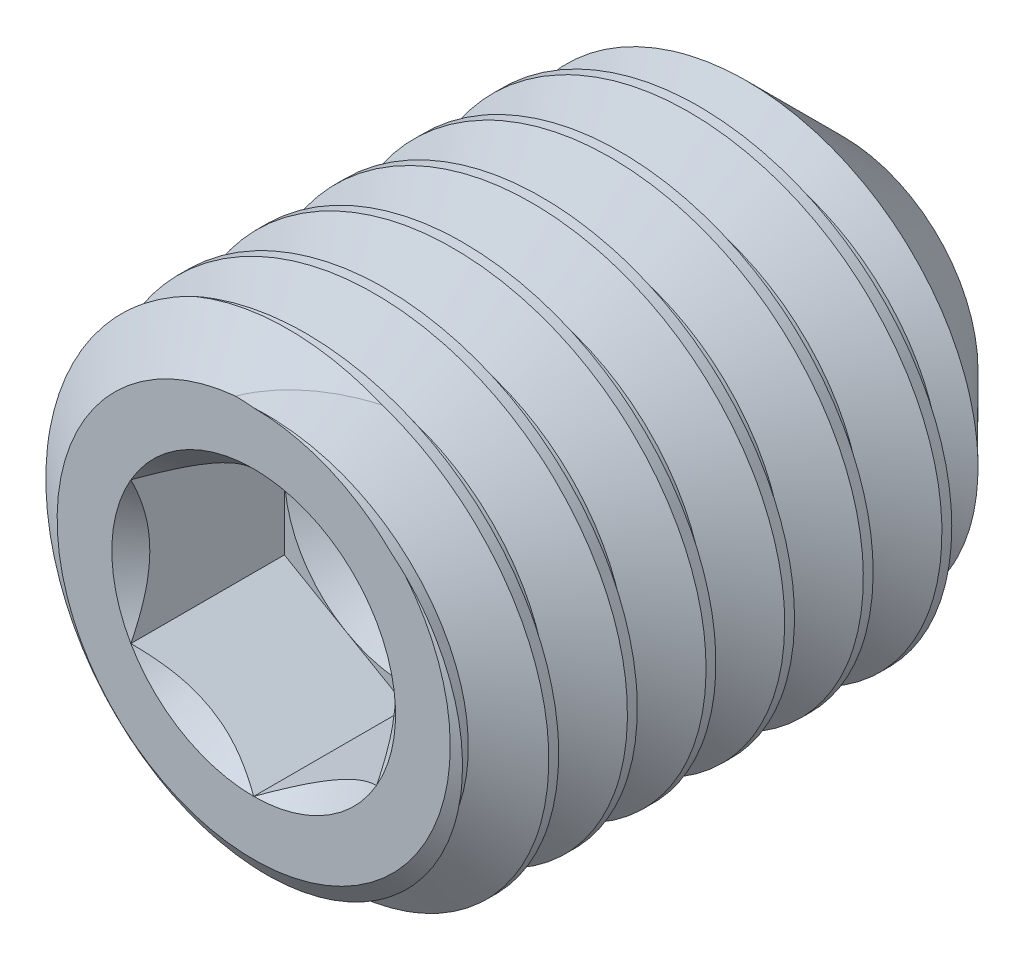
SolidWorks part; units mm, degrees
ref_plane "Front" through (0, 0, 0) normal (0, 0, 1) x (1, 0, 0)
ref_plane "Top" through (0, 0, 0) normal (0, 1, 0) x (1, 0, 0)
ref_plane "Right" through (0, 0, 0) normal (1, 0, 0) x (0, 0, -1)
sketch "Sketch22" plane through (0, 0, 0) normal (1, 0, 0) x (0, 0, -1)
  line L0 (-2.5884, 0) -> (-2.5884, 2)
  line L1 (-2.5884, 2) -> (-2.2383, 2.5)
  line L2 (-2.2383, 2.5) -> (2.2815, 2.5)
  line L3 (2.2815, 2.5) -> (3.4116, 1.3699)
  line L4 (3.4116, 1.3699) -> (2.5884, 0)
  line L5 (2.5884, 0) -> (-2.5884, 0)
  line L6 (2.5884, 0) -> (3.4116, 0) construction
  line L7 (3.4116, 0) -> (3.4116, 1.3699) construction
  line L8 (3.4116, -1.3699) -> (2.5884, 0) construction
  line L9 (-2.2383, -2.5) -> (2.2815, -2.5) construction
  dimension "Dia" = 5
  dimension "Length" = 6
  dimension "D3" = 35
  dimension "D5" = 118
  dimension "D6" = 45
  dimension "D7" = 4
revolve "Revolve1" add sketch "Sketch22" angle 360 about L6
ref_plane "Plane1" through (0, 0, -3.4116) normal (0, 0, 1) x (1, 0, 0)
sketch "Sketch27" plane through (0, 0, -3.4116) normal (0, 0, 1) x (1, 0, 0)
  circle A0 centre (0, 0) radius 2.5 construction
  circle A1 centre (0, 0) radius 2.5
curve "Helix/Spiral1" pitch 0.8 height 6.8 radius 2.5 centre (0, 0, -3.4116) axis (0, 0, 1) start towards (0, 1, 0)
sketch "Sketch28" plane through (0, 0, 0) normal (1, 0, 0) x (0, 0, -1)
  line L0 (3.4116, 2.5) -> (4.1116, 2.5)
  line L1 (4.1116, 2.5) -> (3.8116, 1.9804)
  line L2 (3.8116, 1.9804) -> (3.7116, 1.9804)
  line L3 (3.7116, 1.9804) -> (3.4116, 2.5)
  line L4 (3.5616, 2.2402) -> (3.9616, 2.2402) construction
  line L6 (-2.2383, 2.5) -> (2.2815, 2.5) construction
  dimension "D1" = 0.1
  dimension "D3" = 60
  dimension "D2" = 0.4
sweep "Cut-Sweep2" cut profiles "Sketch28" path "Helix/Spiral1" align with end faces yes
sketch "Sketch23" plane through (0, 0, 2.5884) normal (0, 0, 1) x (1, 0, 0)
  line L1 (0, 1.4434) -> (-1.25, 0.7217)
  line L2 (-1.25, 0.7217) -> (-1.25, -0.7217)
  line L3 (-1.25, -0.7217) -> (0, -1.4434)
  line L4 (0, -1.4434) -> (1.25, -0.7217)
  line L5 (1.25, -0.7217) -> (1.25, 0.7217)
  line L6 (1.25, 0.7217) -> (0, 1.4434)
  circle A0 centre (0, 0) radius 1.25 construction
  dimension "Hex" = 2.5
extrude "Cut-Extrude10" cut sketch "Sketch23" against normal blind 1.5625
sketch "Sketch24" plane through (0, 0, 2.5884) normal (0, 0, 1) x (1, 0, 0)
  circle A0 centre (0, 0) radius 1.4434
extrude "Cut-Extrude11" cut sketch "Sketch24" against normal through all draft 45
sketch "Sketch26" plane through (0, 0, 1.0259) normal (0, 0, 1) x (1, 0, 0)
  circle A0 centre (0, 0) radius 1.25 construction
  circle A1 centre (0, 0) radius 1.25
extrude "Cut-Extrude12" cut sketch "Sketch26" against normal through all draft 60
sketch "Sketch30" plane through (0, 0, 0) normal (1, 0, 0) x (0, 0, -1)
  line L0 (-2.2383, 2.5) -> (2.2815, 2.5) construction
  line L1 (-2.5884, 0) -> (-2.5884, 2) construction
  line L2 (3.4116, 0) -> (3.4116, 1.3699) construction
  line L3 (-2.2383, -2.5) -> (2.2815, -2.5) construction
  point P0 (-2.5884, 2.5)
  point P1 (3.4116, 2.5)
  point P2 (3.4116, -2.5)
  point P11 (2.2116, -2.5)
  dimension "D1" = 1.2
sketch "Sketch31" plane through (0, 0, 0) normal (1, 0, 0) x (0, 0, -1)
  line L2 (2.5884, 0) -> (3.4116, -1.3699)
  line L3 (3.4116, 1.3699) -> (2.5884, 0)
equation "\"D7@Sketch22\"=\"Dia@Sketch22\"*.8"
equation "\"D1@Sketch28\" = \"D4@Helix/Spiral1\" * .125"
equation "\"D2@Sketch28\" = \"D4@Helix/Spiral1\" * .5"
equation "\"D3@Helix/Spiral1\" = \"Length@Sketch22\" + \"D4@Helix/Spiral1\""
equation "\"D1@Sketch30\" = \"D4@Helix/Spiral1\" * 1.5"
equation "\"hex Depth@Cut-Extrude10\" = \"Hex@Sketch23\" * .625"
